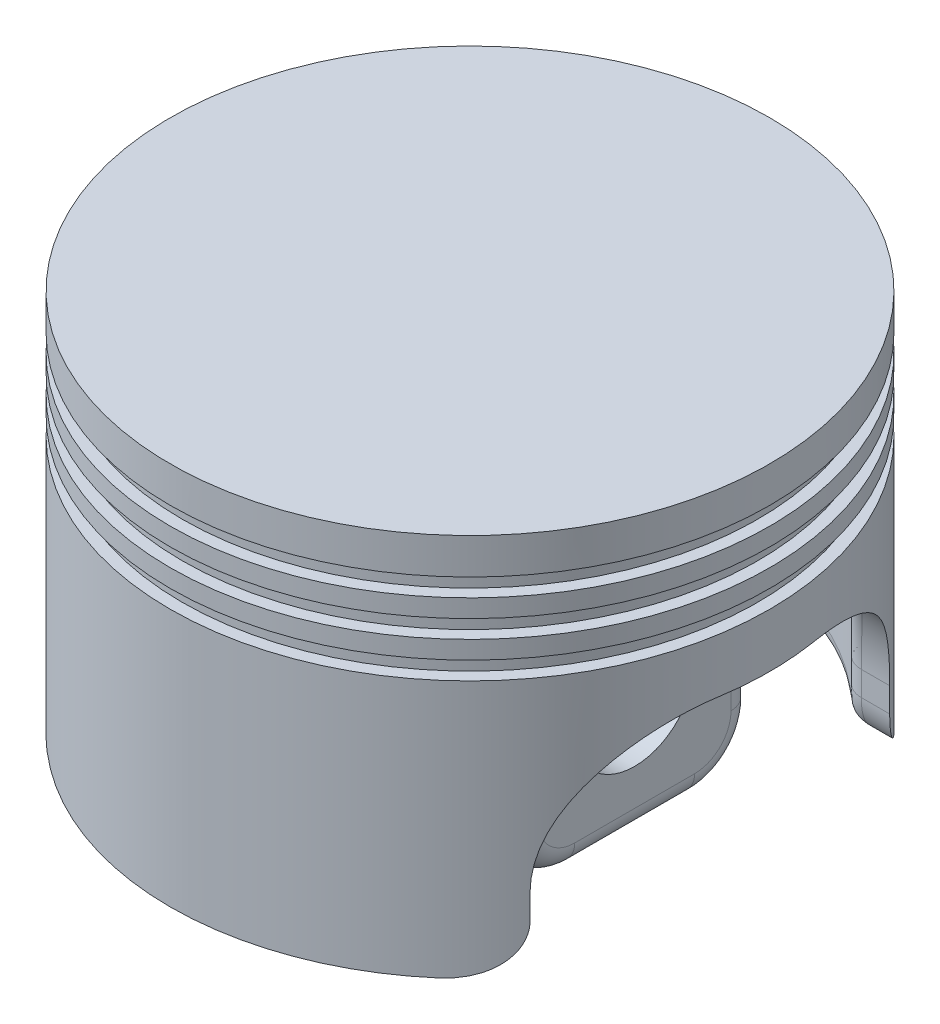
SolidWorks part; units mm, degrees
material "AISI 1035 Steel (SS)"
ref_plane "Front Plane" through (0, 0, 0) normal (0, 0, 1) x (1, 0, 0)
ref_plane "Top Plane" through (0, 0, 0) normal (0, 1, 0) x (1, 0, 0)
ref_plane "Right Plane" through (0, 0, 0) normal (1, 0, 0) x (0, 0, -1)
sketch "Sketch2" plane through (0, 0, 0) normal (1, 0, 0) x (0, 0, -1)
  line L0 (0, 0) -> (63.5, 0)
  line L1 (63.5, 0) -> (63.5, -81.28)
  line L2 (63.5, -81.28) -> (57.15, -81.28)
  line L3 (57.15, -81.28) -> (57.15, -19)
  line L4 (57.15, -19) -> (0, -19)
  line L5 (0, -19) -> (0, 0)
  dimension "D1" = 63.5
  dimension "D2" = 81.28
  dimension "D3" = 6.35
  dimension "D4" = 19
revolve "Revolve1" add sketch "Sketch2" angle 360 about L5
sketch "Sketch4" plane through (0, 0, 0) normal (0, 0, 1) x (1, 0, 0)
  line L0 (63.5, -7.62) -> (60.96, -7.62)
  line L1 (60.96, -7.62) -> (60.96, -11.43)
  line L2 (60.96, -11.43) -> (63.5, -11.43)
  line L3 (63.5, 0) -> (-63.5, 0) construction
  line L4 (63.5, -11.43) -> (63.5, -7.62)
  dimension "D1" = 7.62
  dimension "D2" = 3.81
  dimension "D3" = 2.54
  dimension "D4" = 63.5
ref_axis "Axis1" through (0, 4.064, 0) along (0, -1, 0)
revolve "Cut-Revolve1" cut sketch "Sketch4" angle 360 about axis through (0, 4.064, 0) along (0, -1, 0)
pattern_linear "LPattern1" count 3 spacing 7.62 along (0, -1, 0) of "Cut-Revolve1"
sketch "Sketch5" plane through (0, 0, 0) normal (1, 0, 0) x (0, 0, -1)
  line L0 (0, 4.064) -> (0, -85.344) construction
  line L1 (38.1, -38.1) -> (-38.1, -38.1)
  line L2 (38.1, -38.1) -> (38.1, -81.28)
  line L3 (38.1, -81.28) -> (-38.1, -81.28)
  line L4 (-38.1, -38.1) -> (-38.1, -81.28)
  line L5 (0, -81.28) -> (0, -38.1) construction
  line L6 (38.1, -59.69) -> (-38.1, -59.69) construction
  line L7 (-57.15, -81.28) -> (57.15, -81.28) construction
  line L8 (63.5, 0) -> (-63.5, 0) construction
  point P0 (0, -59.69)
  dimension "D1" = 76.2
  dimension "D2" = 38.1
extrude "Cut-Extrude1" cut sketch "Sketch5" against normal through all both and the other way through all
fillet "Fillet1" radius 28 4 edges at (-46.6985, -38.1, 38.1) (-46.6985, -38.1, -38.1) (46.6985, -38.1, -38.1) (46.6985, -38.1, 38.1)
sketch "Sketch6" plane through (0, -19, 0) normal (0, -1, 0) x (1, 0, 0)
  line L1 (-15.88, 25.4) -> (-34.88, 25.4)
  line L2 (-15.88, 25.4) -> (-15.88, -25.4)
  line L3 (-15.88, -25.4) -> (-34.88, -25.4)
  line L4 (-34.88, 25.4) -> (-34.88, -25.4)
  line L5 (-25.38, -25.4) -> (-25.38, 25.4) construction
  line L6 (-15.88, 0) -> (-34.88, 0) construction
  point P0 (-25.38, 0)
  dimension "D1" = 19
  dimension "D2" = 50.8
  dimension "D3" = 15.88
extrude "Boss-Extrude1" add sketch "Sketch6" along normal blind 63.5
mirror "Mirror1" about plane through (0, 0, 0) normal (1, 0, 0) of "Boss-Extrude1"
sketch "Sketch7" plane through (-34.88, 0, 0) normal (-1, 0, 0) x (0, 0, 1)
  line L0 (25.4, -82.5) -> (-25.4, -82.5) construction
  circle A0 centre (0, -57.1) radius 12.7
  dimension "D1" = 25.4
  dimension "D2" = 25.4
extrude "Cut-Extrude2" cut sketch "Sketch7" against normal through all both and the other way through all
fillet "Fillet2" radius 12.7 4 edges at (25.38, -82.5, -25.4) (25.38, -82.5, 25.4) (-25.38, -82.5, 25.4) (-25.38, -82.5, -25.4)
fillet "Fillet3" radius 10 4 edges at (46.6985, -81.28, -38.1) (46.6985, -81.28, 38.1) (-46.6985, -81.28, 38.1) (-46.6985, -81.28, -38.1)
fillet "Fillet4" radius 5 20 edges at (-34.88, -44.4, 25.4) (-34.88, -78.7803, 21.6803) (-34.88, -44.4, -25.4) (-34.88, -78.7803, -21.6803) (-15.88, -44.4, -25.4) (-15.88, -78.7803, -21.6803) (-15.88, -44.4, 25.4) (-15.88, -78.7803, 21.6803) (34.88, -44.4, 25.4) (34.88, -78.7803, 21.6803) (34.88, -44.4, -25.4) (34.88, -78.7803, -21.6803) (15.88, -44.4, -25.4) (15.88, -78.7803, -21.6803) (15.88, -44.4, 25.4) (15.88, -78.7803, 21.6803) (-34.88, -82.5, 0) (-15.88, -82.5, 0) (34.88, -82.5, 0) (15.88, -82.5, 0)
fillet "Fillet5" radius 5 16 edges at (-57.15, -38.1, 0) (-46.055, -51.2516, 33.8387) (-42.5971, -68.69, 38.1) (-40.0022, -78.1316, 40.816) (0, -81.28, 57.15) (41.3657, -76.2692, 39.4335) (42.5971, -68.69, 38.1) (50.4318, -43.6881, 26.8841) (57.15, -38.1, 0) (46.055, -51.2516, -33.8387) (42.5971, -68.69, -38.1) (40.0022, -78.1316, -40.816) (0, -81.28, -57.15) (-41.3657, -76.2692, -39.4335) (-42.5971, -68.69, -38.1) (-50.4318, -43.6881, -26.8841)
